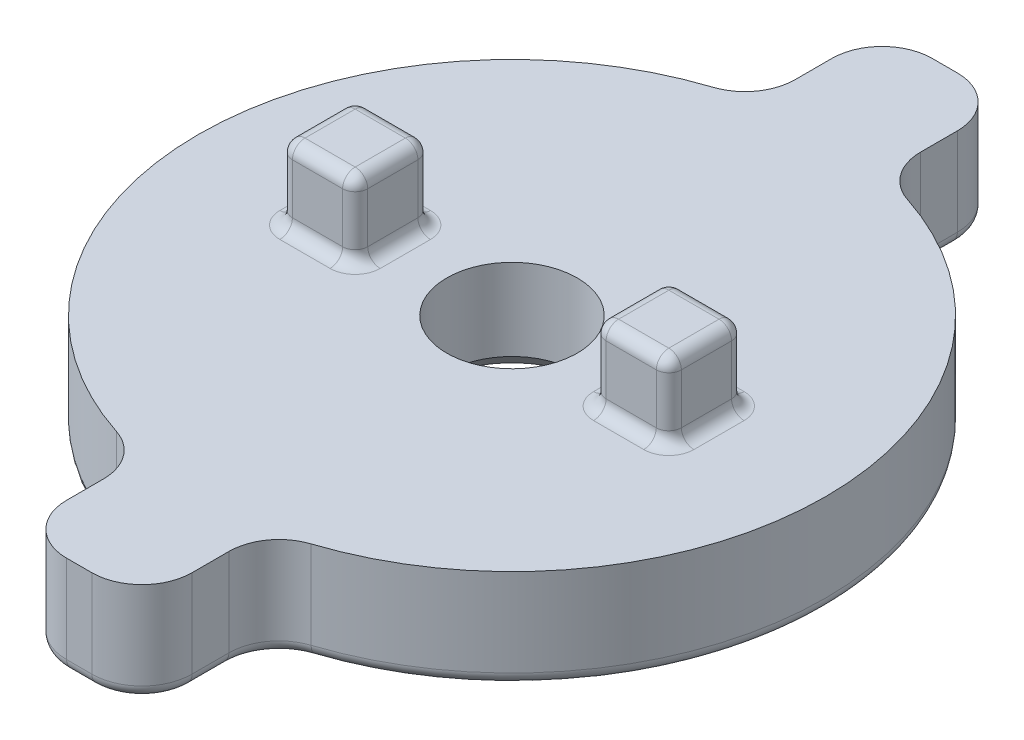
SolidWorks part; units mm, degrees
ref_plane "Front Plane" through (0, 0, 0) normal (0, 0, 1) x (1, 0, 0)
ref_plane "Top Plane" through (0, 0, 0) normal (0, 1, 0) x (1, 0, 0)
ref_plane "Right Plane" through (0, 0, 0) normal (1, 0, 0) x (0, 0, -1)
sketch "Sketch1" plane through (0, 0, 0) normal (0, 1, 0) x (1, 0, 0)
  line L0 (0, 0) -> (12.5, 0) construction
  line L1 (4.75, 1.5) -> (7.75, 1.5)
  line L2 (4.75, 1.5) -> (4.75, -1.5)
  line L3 (4.75, -1.5) -> (7.75, -1.5)
  line L4 (7.75, 1.5) -> (7.75, -1.5)
  line L5 (4.75, 1.5) -> (7.75, -1.5) construction
  line L6 (4.75, -1.5) -> (7.75, 1.5) construction
  line L7 (-2.5, 13.784) -> (-2.5, 15.2474)
  line L8 (-0.5, 17.2474) -> (0.5, 17.2474)
  line L9 (2.5, 15.2474) -> (2.5, 13.784)
  line L10 (-2.5, 12.2474) -> (2.5, 12.2474) construction
  line L11 (2.5, -15.2474) -> (2.5, -13.784)
  line L12 (-0.5, -17.2474) -> (0.5, -17.2474)
  line L13 (-2.5, -13.784) -> (-2.5, -15.2474)
  line L14 (0, 5.5827) -> (0, -4.8309) construction
  line L15 (-7.75, 1.5) -> (-7.75, -1.5)
  line L16 (-4.75, -1.5) -> (-7.75, -1.5)
  line L17 (-4.75, 1.5) -> (-4.75, -1.5)
  line L18 (-4.75, 1.5) -> (-7.75, 1.5)
  arc A0 (-3.8793, 11.8828) -> (-3.8793, -11.8828) centre (0, 0) ccw
  arc A1 (3.8793, -11.8828) -> (3.8793, 11.8828) centre (0, 0) ccw
  circle A2 centre (0, 0) radius 1.85
  arc A3 (-2.5, -13.784) -> (-3.8793, -11.8828) centre (-4.5, -13.784) ccw
  arc A4 (2.5, -13.784) -> (3.8793, -11.8828) centre (4.5, -13.784) cw
  arc A5 (2.5, 13.784) -> (3.8793, 11.8828) centre (4.5, 13.784) ccw
  arc A6 (-2.5, 13.784) -> (-3.8793, 11.8828) centre (-4.5, 13.784) cw
  arc A7 (-0.5, -17.2474) -> (-2.5, -15.2474) centre (-0.5, -15.2474) cw
  arc A8 (0.5, -17.2474) -> (2.5, -15.2474) centre (0.5, -15.2474) ccw
  arc A9 (2.5, 15.2474) -> (0.5, 17.2474) centre (0.5, 15.2474) ccw
  arc A10 (-2.5, 15.2474) -> (-0.5, 17.2474) centre (-0.5, 15.2474) cw
  point P3 (6.25, 0)
  point P8 (6.25, 0)
  point P12 (0, 12.2474)
  point P27 (-2.5, -12.2474)
  point P30 (2.5, -12.2474)
  point P39 (-2.5, -17.2474)
  point P42 (2.5, -17.2474)
  point P45 (2.5, 17.2474)
  point P48 (-2.5, 17.2474)
  dimension "D1" = 25
  dimension "D5" = 3.7
  dimension "D6" = 2
  dimension "D2" = 3
  dimension "D3" = 5
  dimension "D4" = 5
extrude "Boss-Extrude1" add sketch "Sketch1" against normal blind 4 contours L11 A1 L9 L8 L7 A0 L13 L12 L1 L4 L3 L2 L18 L17 L16 L15 | L17 L18 L15 L16 | L4 L1 L2 L3 region at (6.25, 0, 0) region at (-2.074, 0, -14.5157) region at (-6.25, 0, 0)
extrude "Boss-Extrude2" add sketch "Sketch1<3>" along normal blind 3 contours L17 L18 L15 L16 | L4 L1 L2 L3 region at (6.25, 0, 0) region at (-6.25, 0, 0)
sketch "Sketch1<3>" plane through (0, 0, 0) normal (0, 1, 0) x (1, 0, 0) same geometry as "Sketch1"
chamfer "Chamfer1" distance 1.5 angle 45 1 edges at (0, -4, 1.85)
sketch "Sketch2" plane through (0, -4, 0) normal (0, -1, 0) x (1, 0, 0)
  circle A0 centre (0, 0) radius 2.6
  dimension "D1" = 5.2
extrude "Cut-Extrude1" cut sketch "Sketch2" against normal up to surface (4 mm away) contours A0 up to face at (6.25, 0, 0)
fillet "Fillet1" radius 0.5 40 edges at (-2.8811, -4, -12.6096) (-2.5, -4, -14.5157) (-1.9142, -4, -16.6617) (0, -4, -17.2474) (1.9142, -4, -16.6617) (2.5, -4, -14.5157) (2.8811, -4, -12.6096) (12.5, -4, 0) (2.8811, -4, 12.6096) (2.5, -4, 14.5157) (1.9142, -4, 16.6617) (0, -4, 17.2474) (-1.9142, -4, 16.6617) (-2.5, -4, 14.5157) (-2.8811, -4, 12.6096) (-12.5, -4, 0) (6.25, 3, -1.5) (6.25, 0, -1.5) (4.75, 1.5, -1.5) (4.75, 3, 0) (4.75, 0, 0) (-6.25, 3, -1.5) (-6.25, 0, -1.5) (-7.75, 1.5, -1.5) (-7.75, 3, 0) (-7.75, 0, 0) (7.75, 3, 0) (7.75, 1.5, -1.5) (7.75, 0, 0) (4.75, 1.5, 1.5) (6.25, 3, 1.5) (7.75, 1.5, 1.5) (6.25, 0, 1.5) (-4.75, 3, 0) (-4.75, 1.5, -1.5) (-4.75, 0, 0) (-7.75, 1.5, 1.5) (-6.25, 3, 1.5) (-4.75, 1.5, 1.5) (-6.25, 0, 1.5)
